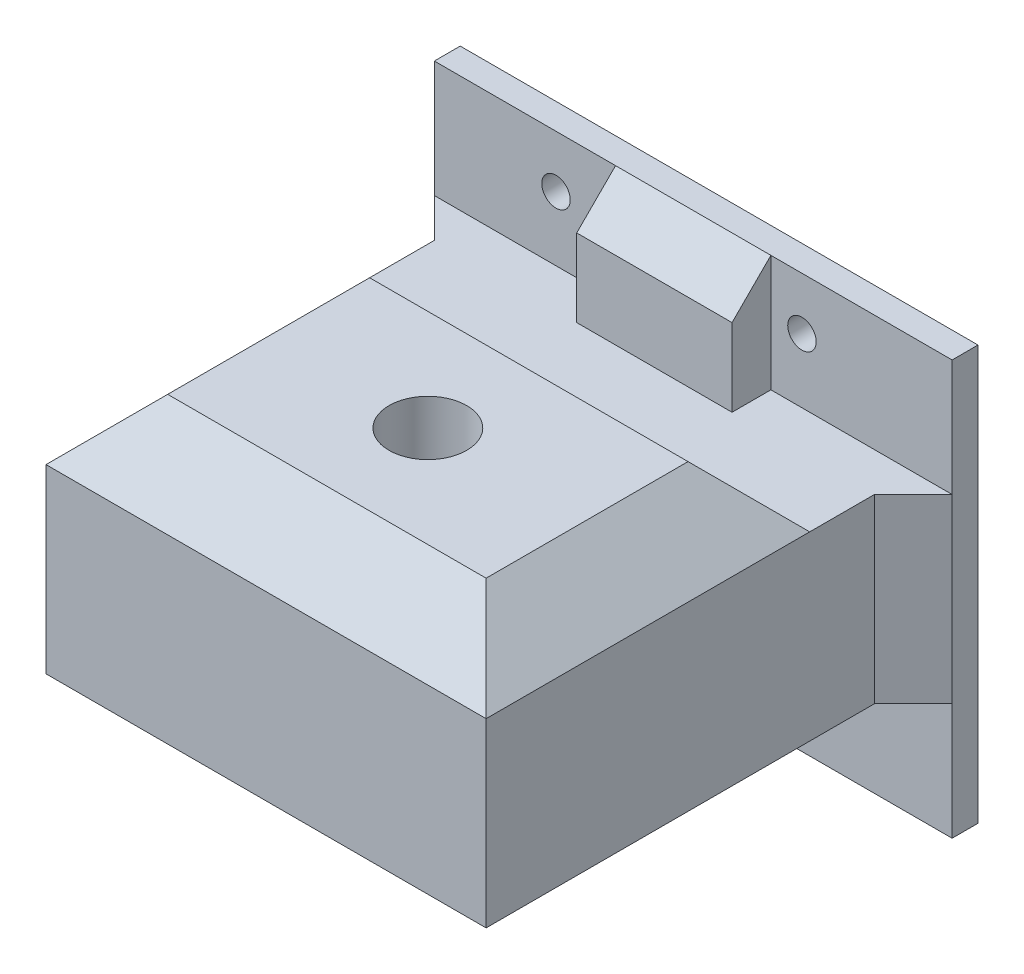
SolidWorks part; units mm, degrees
ref_plane "Piano frontale" through (0, 0, 0) normal (0, 0, 1) x (1, 0, 0)
ref_plane "Piano superiore" through (0, 0, 0) normal (0, 1, 0) x (1, 0, 0)
ref_plane "Piano destro" through (0, 0, 0) normal (1, 0, 0) x (0, 0, -1)
sketch "Schizzo21" plane through (0, 0, 0) normal (0, 0, -1) x (-1, 0, 0)
  line L8 (-682, 347.72) -> (-682, 187.72)
  line L9 (-682, 187.72) -> (-482, 187.72)
  line L10 (-482, 187.72) -> (-482, 347.72)
  line L11 (-482, 347.72) -> (-682, 347.72)
  circle A0 centre (-529, 327.5) radius 5.5
  circle A1 centre (-529, 216.5) radius 5.5
  circle A2 centre (-624, 216.5) radius 5.5
  circle A3 centre (-624, 327.5) radius 5.5
  point P2 (0, 0)
  point P4 (0, 0)
  point P6 (0, 0)
  dimension "D1" = 111
  dimension "D2" = 111
  dimension "D3" = 95
  dimension "D4" = 95
  dimension "D5" = 20.22
  dimension "D6" = 160
extrude "Estrusione-Estrusione1" add sketch "Schizzo21" along normal blind 10
sketch "Schizzo22" plane through (0, 0, 0) normal (0, 0, 1) x (1, 0, 0)
  line L0 (482, 187.72) -> (482, 347.72) construction
  line L1 (482, 302.72) -> (552, 302.72)
  line L2 (482, 302.72) -> (482, 232.72)
  line L3 (482, 232.72) -> (552, 232.72)
  line L4 (682, 302.72) -> (682, 232.72)
  line L5 (682, 347.72) -> (682, 187.72) construction
  line L6 (482, 347.72) -> (682, 347.72) construction
  line L7 (552, 347.72) -> (612, 347.72)
  line L8 (552, 347.72) -> (552, 302.72)
  line L9 (552, 187.72) -> (612, 187.72)
  line L10 (612, 347.72) -> (612, 302.72)
  line L11 (682, 187.72) -> (482, 187.72) construction
  line L12 (612, 302.72) -> (682, 302.72)
  line L13 (552, 232.72) -> (552, 187.72)
  line L14 (612, 232.72) -> (682, 232.72)
  line L15 (612, 232.72) -> (612, 187.72)
  dimension "D1" = 70
  dimension "D2" = 70
  dimension "D3" = 45
  dimension "D4" = 45
extrude "Estrusione-Estrusione2" add sketch "Schizzo22" along normal blind 15
chamfer "Smusso1" distance 15 angle 45 4 edges at (682, 267.72, 15) (582, 347.72, 15) (582, 187.72, 15) (482, 267.72, 15)
sketch "Schizzo23" plane through (0, 0, 15) normal (0, 0, 1) x (1, 0, 0)
  line L1 (497, 302.72) -> (667, 302.72)
  line L2 (497, 302.72) -> (497, 232.72)
  line L3 (497, 232.72) -> (667, 232.72)
  line L4 (667, 302.72) -> (667, 232.72)
extrude "Estrusione-Estrusione3" add sketch "Schizzo23" along normal blind 150
sketch "Schizzo24" plane through (0, 302.72, 0) normal (0, 1, 0) x (1, 0, 0)
  line L1 (497, -165) -> (667, -165)
  line L2 (497, -165) -> (497, -40)
  line L3 (497, -40) -> (667, -40)
  line L4 (667, -165) -> (667, -40)
  dimension "D1" = 125
extrude "Estrusione-Estrusione4" add sketch "Schizzo24" along normal blind 23.5
chamfer "Smusso5" distance 23.5 angle 45 4 edges at (667, 326.22, 102.5) (582, 326.22, 40) (582, 326.22, 165) (497, 326.22, 102.5)
ref_plane "Piano1" through (0, 267.72, 0) normal (0, -1, 0) x (-1, 0, 0)
mirror "Specchia1" about plane through (0, 267.72, 0) normal (0, -1, 0) of "Estrusione-Estrusione4", "Smusso5"
sketch "Schizzo26" plane through (0, 326.22, 0) normal (0, 1, 0) x (1, 0, 0)
  line L0 (520.5, -63.5) -> (643.5, -141.5) construction
  line L1 (643.5, -141.5) -> (643.5, -62.9318) construction
  line L2 (643.5, -62.9318) -> (520.5, -141.5) construction
  circle A0 centre (582, -102.5) radius 15
  dimension "D1" = 30
extrude "Taglio-Estrusione1" cut sketch "Schizzo26" against normal up to surface (117 mm away) contours A0 up to face at (582, 209.22, 102.5)
